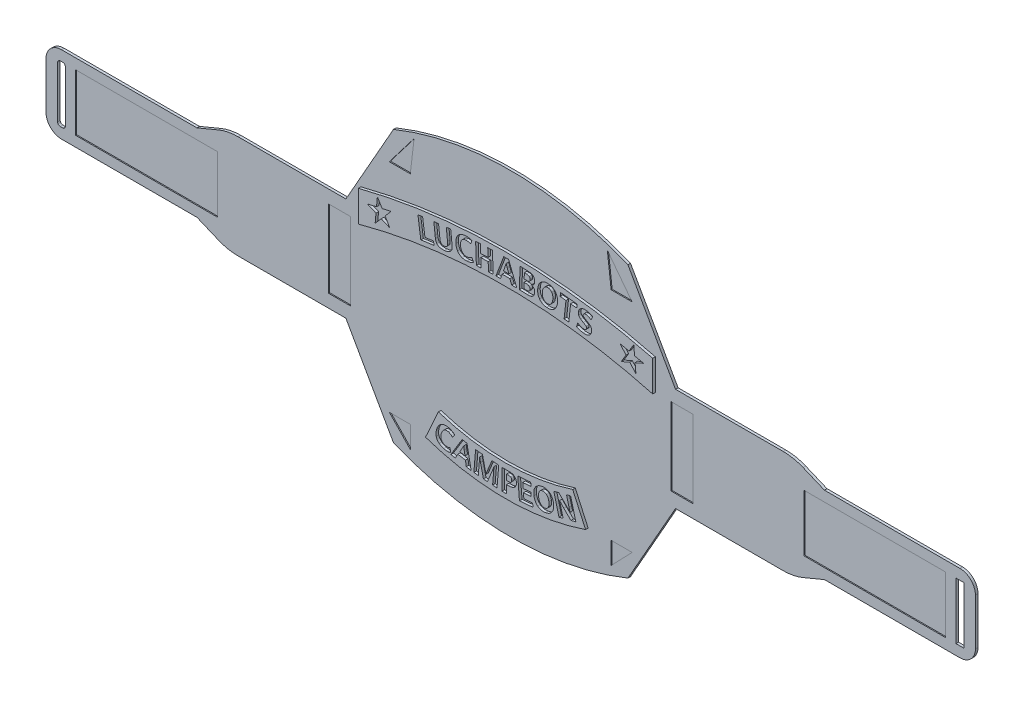
SolidWorks part; units mm, degrees
ref_plane "Alzado" through (0, 0, 0) normal (0, 0, 1) x (1, 0, 0)
ref_plane "Planta" through (0, 0, 0) normal (0, 1, 0) x (1, 0, 0)
ref_plane "Vista lateral" through (0, 0, 0) normal (1, 0, 0) x (0, 0, -1)
sketch "Croquis1" plane through (0, 0, 0) normal (0, 0, 1) x (1, 0, 0)
  line L0 (-13, 2.0625) -> (13, 2.0625) construction
  line L1 (0, 0) -> (0, -6) construction
  line L2 (-15.5, -3.4285) -> (-13, 2.0625)
  line L3 (13, 2.0625) -> (15.5, -3.4285)
  arc A0 (-13, 2.0625) -> (13, 2.0625) centre (0, 42) ccw
  arc A1 (-15.5, -3.4285) -> (15.5, -3.4285) centre (0, 42) ccw
  arc A2 (-15.1223, -2.599) -> (15.1223, -2.599) centre (0, 42) ccw construction
  text T0 "<b>CAMPEON</b>" font "Siemens Sans Black" height 4
  dimension "D4" = 42
  dimension "D1" = 6
  dimension "D2" = 26
  dimension "D3" = 31
extrude "Saliente-Extruir2" add sketch "Croquis1" along normal blind 0.5 contours L2 A1 L3 A0
sketch "Croquis3" plane through (0, 0, 0.5) normal (0, 0, 1) x (1, 0, 0)
  arc A0 (-15.1223, -2.599) -> (15.1223, -2.599) centre (0, 42) ccw construction
  arc A1 (-15.1223, -2.599) -> (15.1223, -2.599) centre (0, 42) ccw construction
  text T0 "CAMPEON" font "Siemens Sans Black" height 4
extrude "Cortar-Extruir1" cut sketch "Croquis3" against normal through all
sketch "Croquis4" plane through (0, 0, 0) normal (0, 0, 1) x (1, 0, 0)
  line L0 (0, 0) -> (0, -6) construction
  arc A0 (-15.5, -3.4285) -> (15.5, -3.4285) centre (0, 42) ccw construction
sketch "Croquis6" plane through (0, 0, 0) normal (0, 0, -1) x (-1, 0, 0)
  line L0 (28.5, 31.8151) -> (28.5, 25.8151) construction
  line L1 (-28.5, 31.8151) -> (-28.5, 25.8151) construction
  line L2 (28.5, 31.8151) -> (28.5, 25.8151)
  line L3 (-28.5, 25.8151) -> (-28.5, 31.8151)
  line L4 (28.5, 25.8151) -> (-28.5, 25.8151) construction
  line L5 (-28.5, 31.8151) -> (28.5, 31.8151) construction
  line L6 (0, 35.4268) -> (0, 29.6268) construction
  line L7 (-28.5, 3.8151) -> (-28.5, 25.8151) construction
  arc A0 (28.5, 25.8151) -> (-28.5, 25.8151) centre (0, -78.8252) ccw
  arc A1 (28.5, 31.8151) -> (-28.5, 31.8151) centre (0, -78.8252) ccw
  dimension "D1" = 6
  dimension "D2" = 5.8
extrude "Saliente-Extruir3" add sketch "Croquis6" against normal up to surface (0.5 mm away) separate body up to face at (4.0851, -2.8736, 0.5)
sketch "Croquis7" plane through (0, 0, 0.5) normal (0, 0, 1) x (1, 0, 0)
  line L0 (-28.5, 31.8151) -> (-28.5, 25.8151) construction
  line L1 (28.5, 25.8151) -> (28.5, 31.8151) construction
  line L2 (-28.5, 25.8151) -> (-28.5, 31.8151) construction
  arc A0 (-28.5, 26.6651) -> (28.5, 26.6651) centre (0, -78.8252) cw construction
  text T0 "LUCHABOTS" font "Siemens Sans Black" height 4
  dimension "D1" = 0.85
extrude "Cortar-Extruir2" cut sketch "Croquis7" against normal through all
sketch "Croquis8" plane through (0, 0, 0.5) normal (0, 0, 1) x (1, 0, 0)
  line L0 (-28.5, 31.8151) -> (-28.5, 25.8151) construction
  line L1 (25.2523, 27.5747) -> (26.7386, 30.072)
  line L2 (26.7386, 30.072) -> (24.8228, 32.2573)
  line L3 (24.8228, 32.2573) -> (22.1524, 31.1105)
  line L4 (22.1524, 31.1105) -> (22.4179, 28.2165)
  line L5 (22.4179, 28.2165) -> (25.2523, 27.5747)
  line L6 (28.5, 25.8151) -> (28.5, 31.8151) construction
  line L7 (22.4179, 28.2165) -> (24.8228, 32.2573)
  line L8 (25.2523, 27.5747) -> (22.1524, 31.1105)
  line L9 (26.7386, 30.072) -> (22.4179, 28.2165)
  line L10 (22.1524, 31.1105) -> (26.7386, 30.072)
  line L11 (24.8228, 32.2573) -> (25.2523, 27.5747)
  line L12 (0, 35.4268) -> (0, 29.6268) construction
  line L13 (28.5, 31.8151) -> (28.5, 25.8151) construction
  circle A0 centre (24.2768, 29.8462) radius 2 construction
  arc A1 (-28.5, 28.8151) -> (28.5, 28.8151) centre (0, -78.7457) cw construction
  point P14 (0, 32.5268)
  dimension "D1" = 4
extrude "Cortar-Extruir3" cut sketch "Croquis8" against normal through all both and the other way through all contours L11 L9 L8 | L10 L11 L9 | L11 L10 L7 L8 L9 | L11 L7 L10 | L10 L8 L7 | L9 L8 L7
mirror "Simetría1" about plane through (0, 0, 0) normal (1, 0, 0) of "Cortar-Extruir3"
sketch "Croquis9" plane through (0, 0, -0.5) normal (0, 0, -1) x (-1, 0, 0)
  line L0 (22.7037, 44.0957) -> (-22.7037, 44.0957) construction
  line L5 (0, 44.0957) -> (0, 17.8151) construction
  line L6 (13.2764, 48.5571) -> (-13.2764, 48.5571) construction
  line L8 (22.7037, 44.0957) -> (31.9191, 27.8151)
  line L12 (0, 17.8151) -> (0, -11.4429) construction
  line L13 (31.9191, 27.8151) -> (54.7858, 27.8151)
  line L14 (54.7858, 27.8151) -> (60.764, 25.3151)
  line L15 (60.764, 25.3151) -> (90, 25.3151)
  line L16 (90, 25.3151) -> (90, 10.3151)
  line L17 (90, 17.8151) -> (0, 17.8151) construction
  line L18 (-22.7037, 44.0957) -> (-31.9191, 27.8151)
  line L19 (-54.7858, 27.8151) -> (-60.764, 25.3151)
  line L20 (-31.9191, 27.8151) -> (-54.7858, 27.8151)
  line L21 (-90, 25.3151) -> (-90, 10.3151)
  line L22 (-60.764, 25.3151) -> (-90, 25.3151)
  line L23 (-60.764, 10.3151) -> (-90, 10.3151)
  line L24 (-54.7858, 7.8151) -> (-60.764, 10.3151)
  line L25 (-31.9191, 7.8151) -> (-54.7858, 7.8151)
  line L26 (-22.7037, -8.4656) -> (-31.9191, 7.8151)
  line L27 (22.7037, -8.4656) -> (31.9191, 7.8151)
  line L28 (31.9191, 7.8151) -> (54.7858, 7.8151)
  line L29 (54.7858, 7.8151) -> (60.764, 10.3151)
  line L30 (60.764, 10.3151) -> (90, 10.3151)
  arc A0 (-22.7037, 44.0957) -> (22.7037, 44.0957) centre (0, -11.4429) cw
  arc A1 (-22.7037, -8.4656) -> (22.7037, -8.4656) centre (0, 47.073) ccw
  point P0 (0, 17.8151)
  point P2 (0, 49.3981)
  point P14 (0, 48.5571)
  point P23 (-90, 17.8151)
  point P33 (0, 0)
  point P34 (22.7037, 44.0957)
  dimension "D3" = 90
  dimension "D1" = 60
  dimension "D4" = 7.5
  dimension "D5" = 10
extrude "Saliente-Extruir5" add sketch "Croquis9" along normal blind 0.5
fillet "Redondeo1" radius 3 4 edges at (-90, 10.3151, -0.75) (-90, 25.3151, -0.75) (90, 10.3151, -0.75) (90, 25.3151, -0.75)
sketch "Croquis10" plane through (0, 0, -0.5) normal (0, 0, 1) x (1, 0, 0)
  line L0 (-90, 17.8151) -> (-87, 17.8151) construction
  line L1 (-90, 22.3151) -> (-90, 13.3151) construction
  line L3 (-87.75, 23.3151) -> (-86.25, 23.3151)
  line L4 (-87.75, 23.3151) -> (-87.75, 12.3151)
  line L5 (-87.75, 12.3151) -> (-86.25, 12.3151)
  line L6 (-86.25, 23.3151) -> (-86.25, 12.3151)
  line L7 (-87.75, 23.3151) -> (-86.25, 12.3151) construction
  line L8 (-87.75, 12.3151) -> (-86.25, 23.3151) construction
  dimension "D1" = 11
  dimension "D2" = 1.5
  dimension "D3" = 3
extrude "Cortar-Extruir4" cut sketch "Croquis10" against normal through all
fillet "Redondeo2" radius 0.5 4 edges at (-87.75, 12.3151, -0.75) (-86.25, 12.3151, -0.75) (-86.25, 23.3151, -0.75) (-87.75, 23.3151, -0.75)
fillet "Redondeo3" radius 10 4 edges at (54.7858, 27.8151, -0.75) (54.7858, 7.8151, -0.75) (-54.7858, 7.8151, -0.75) (-54.7858, 27.8151, -0.75)
mirror "Simetría5" about plane through (0, 0, 0) normal (1, 0, 0) of "Cortar-Extruir4"
sketch "Croquis11" plane through (0, 0, -0.5) normal (0, 0, 1) x (1, 0, 0)
  line L0 (-84.25, 12.3151) -> (-84.25, 10.3151) construction
  line L1 (-84.25, 12.3151) -> (-56.764, 12.3151)
  line L2 (-84.25, 12.3151) -> (-84.25, 23.3151)
  line L3 (-84.25, 23.3151) -> (-56.764, 23.3151)
  line L4 (-56.764, 12.3151) -> (-56.764, 23.3151)
  line L5 (-35.264, 25.3151) -> (-31, 25.3151)
  line L6 (-35.264, 25.3151) -> (-35.264, 10.3151)
  line L7 (-35.264, 10.3151) -> (-31, 10.3151)
  line L8 (-31, 25.3151) -> (-31, 10.3151)
  line L9 (-60.764, 10.3151) -> (-87, 10.3151) construction
  line L10 (-56.764, 12.3151) -> (-56.764, 10.3151) construction
  line L11 (-84.25, 23.3151) -> (-84.25, 25.3151) construction
  line L12 (-60.764, 25.3151) -> (-87, 25.3151) construction
  line L13 (-56.764, 23.3151) -> (-54.764, 23.3151) construction
  line L14 (-54.764, 25.3151) -> (-54.764, 10.3151) construction
  line L16 (-86.25, 17.8151) -> (-84.25, 17.8151) construction
  line L17 (-86.25, 12.8151) -> (-86.25, 22.8151) construction
  line L18 (-35.264, 25.3151) -> (-37.764, 25.3151) construction
  line L19 (-37.764, 25.3151) -> (-35.264, 25.3151) construction
  line L20 (-35.264, 27.8151) -> (-35.264, 25.3151) construction
  line L21 (-31.9191, 27.8151) -> (-52.779, 27.8151) construction
  line L22 (-31.9191, 7.8151) -> (-31.9191, 10.3151) construction
  line L23 (-31.9191, 10.3151) -> (-31, 10.3151) construction
  line L24 (-31, 10.3151) -> (-28.5, 10.3151) construction
  line L25 (-28.5, 25.8151) -> (-28.5, 3.8151) construction
  line L26 (-23.5135, 38.2681) -> (-19.4485, 38.2681)
  line L27 (-19.4485, 38.2681) -> (-18.7133, 44.5386)
  line L28 (-18.7133, 44.5386) -> (-23.5135, 38.2681)
  line L29 (-23.5135, -3.7497) -> (-19.4485, -7.9712)
  line L30 (-19.4485, -7.9712) -> (-19.4485, -3.7497)
  line L31 (-19.4485, -3.7497) -> (-23.5135, -3.7497)
  dimension "D1" = 2
extrude "Cortar-Extruir5" cut sketch "Croquis11" against normal blind 0.2
mirror "Simetría6" about plane through (0, 0, 0) normal (1, 0, 0) of "Cortar-Extruir5"
